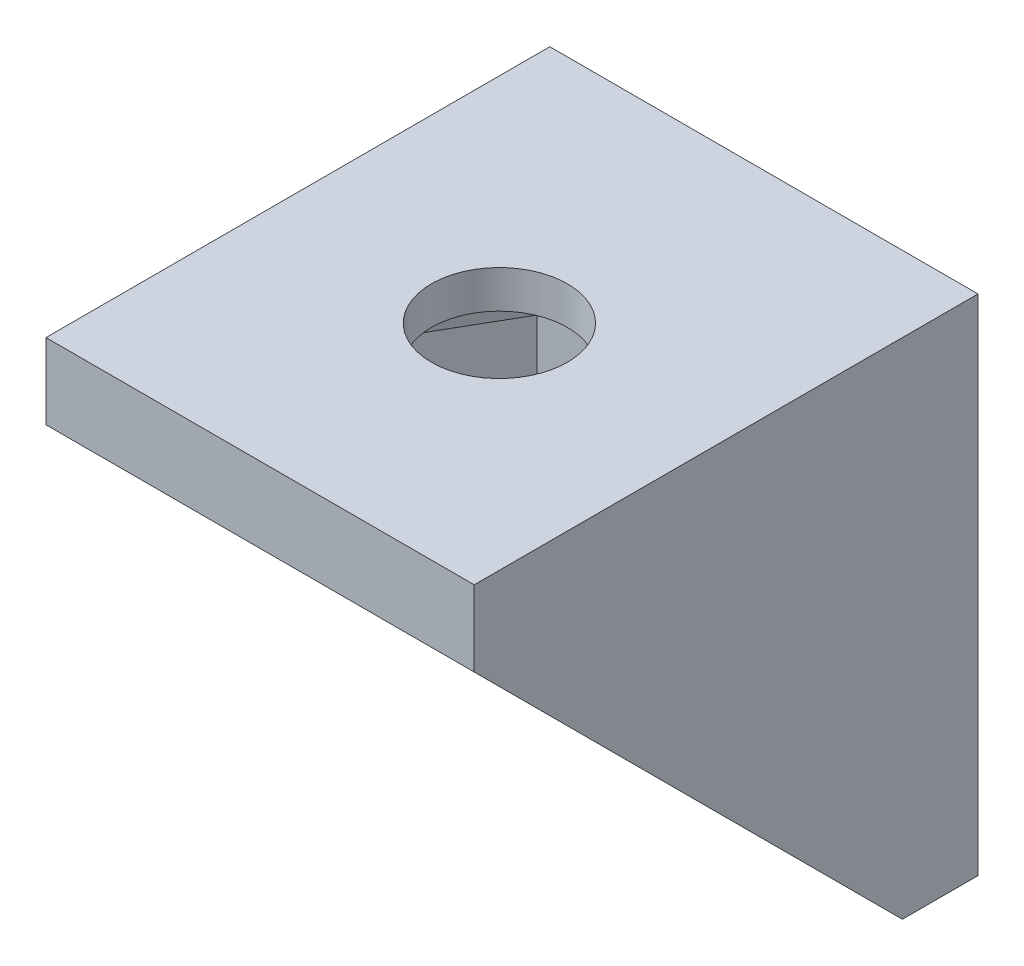
SolidWorks part; units mm, degrees
material "1060 Alloy"
ref_plane "Front Plane" through (0, 0, 0) normal (0, 0, 1) x (1, 0, 0)
ref_plane "Top Plane" through (0, 0, 0) normal (0, 1, 0) x (1, 0, 0)
ref_plane "Right Plane" through (0, 0, 0) normal (1, 0, 0) x (0, 0, -1)
sketch "Sketch1" plane through (0, 0, 0) normal (1, 0, 0) x (0, 0, -1)
  line L0 (0, 0) -> (-20, 0)
  line L1 (-20, 0) -> (-20, -3)
  line L2 (-20, -3) -> (-11.5, -11.5)
  line L3 (-11.5, -11.5) -> (0, 0) construction
  line L4 (-3, -20) -> (-11.5, -11.5)
  line L5 (0, -20) -> (-3, -20)
  line L6 (0, 0) -> (0, -20)
  dimension "D1" = 3
  dimension "D2" = 20
extrude "Boss-Extrude1" add sketch "Sketch1" along normal mid plane 17
sketch "Sketch2" plane through (0, 0, 0) normal (1, 0, 0) x (0, 0, -1)
  line L0 (-20, -3) -> (-3, -20) construction
  line L1 (-3, -3) -> (-20, -3)
  line L2 (-3, -3) -> (-3, -20)
  line L3 (-3, -20) -> (-20, -20)
  line L4 (-20, -3) -> (-20, -20)
  line L5 (-20, 0) -> (-20, -3) construction
extrude "Cut-Extrude1" cut sketch "Sketch2" against normal mid plane 12
sketch "Sketch3" plane through (0, 0, 3) normal (0, 0, 1) x (1, 0, 0)
  line L0 (0, -9) -> (0, -12) construction
  line L1 (-3, -9) -> (-3, -12)
  line L2 (3, -9) -> (3, -12)
  line L3 (0, -10.5) -> (0.7454, -10.5) construction
  line L4 (-6, -20) -> (6, -20) construction
  arc A0 (-3, -9) -> (3, -9) centre (0, -9) cw
  arc A1 (-3, -12) -> (3, -12) centre (0, -12) ccw
  dimension "D3" = 9
  dimension "D4" = 5
  dimension "D1" = 3
  dimension "D2" = 3
extrude "Cut-Extrude2" cut sketch "Sketch3" against normal up to next
sketch "Esboço1" plane through (0, 0, 0) normal (0, 1, 0) x (1, 0, 0)
  circle A2 centre (0, -10.5) radius 2.7
extrude "Corte-extrusão1" cut sketch "Esboço1" against normal up to next
sketch "Esboço3" plane through (0, -3, 0) normal (0, -1, 0) x (1, 0, 0)
  line L4 (6, 3) -> (6, 20)
  line L5 (6, 20) -> (-6, 20)
  line L6 (-6, 20) -> (-6, 3)
  line L7 (-6, 3) -> (6, 3)
  line L8 (6, 3) -> (6, 20)
  line L9 (6, 20) -> (-6, 20)
  line L10 (-6, 20) -> (-6, 3)
  line L11 (-6, 3) -> (6, 3)
  line L32 (0, 14.7) -> (-2.4249, 14.7)
  line L33 (-2.4249, 14.7) -> (-3.6373, 12.6)
  line L34 (-3.6373, 12.6) -> (-4.8497, 10.5)
  line L35 (-4.8497, 10.5) -> (-3.6373, 8.4)
  line L36 (-3.6373, 8.4) -> (-2.4249, 6.3)
  line L37 (-2.4249, 6.3) -> (0, 6.3)
  line L38 (0, 6.3) -> (2.4249, 6.3)
  line L39 (2.4249, 6.3) -> (3.6373, 8.4)
  line L40 (3.6373, 8.4) -> (4.8497, 10.5)
  line L41 (4.8497, 10.5) -> (3.6373, 12.6)
  line L42 (3.6373, 12.6) -> (2.4249, 14.7)
  line L43 (2.4249, 14.7) -> (0, 14.7)
  dimension "D1" = 0
extrude "Corte-extrusão2" cut sketch "Esboço3" against normal blind 1.5 contours L32 L33 L34 L35 L36 L37 L38 L39 L40 L41 L42 L43
